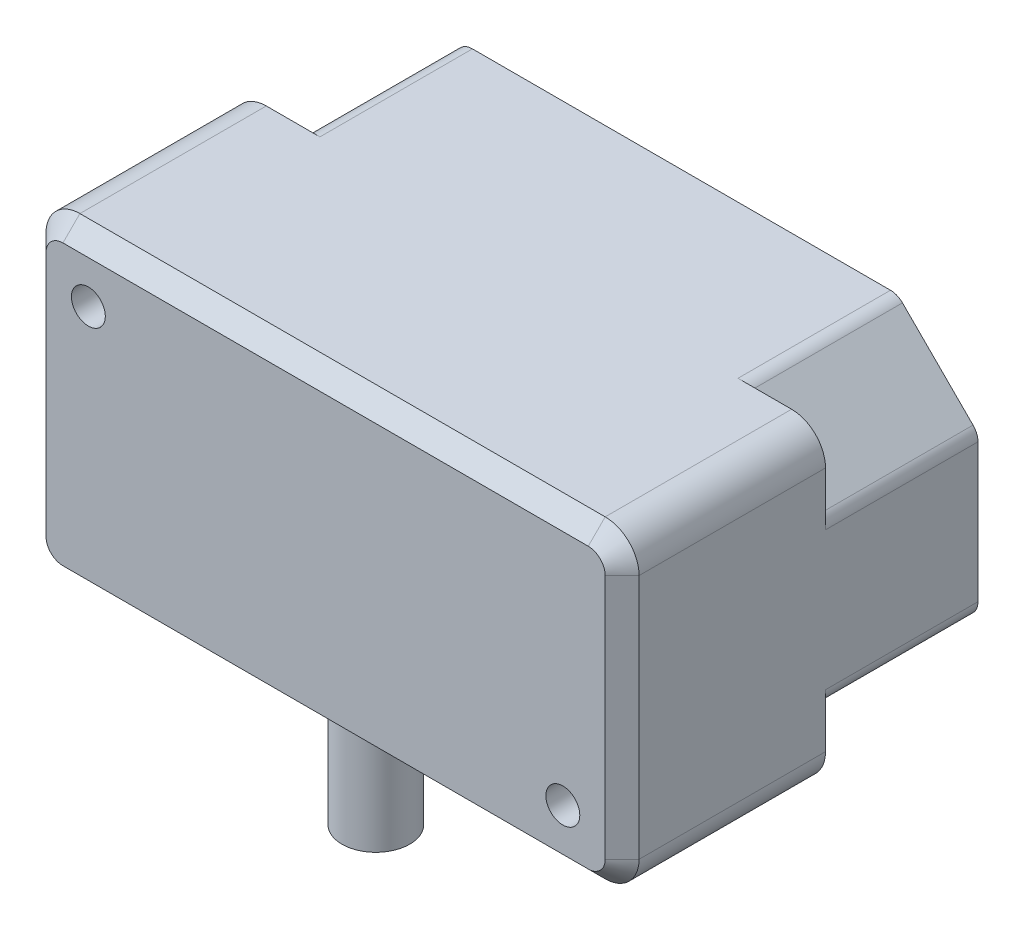
SolidWorks part; units mm, degrees
material "ABS"
ref_plane "Plan de face" through (0, 0, 0) normal (0, 0, 1) x (1, 0, 0)
ref_plane "Plan de dessus" through (0, 0, 0) normal (0, 1, 0) x (1, 0, 0)
ref_plane "Plan de droite" through (0, 0, 0) normal (1, 0, 0) x (0, 0, -1)
sketch "Esquisse1" plane through (0, 0, 0) normal (0, 0, 1) x (1, 0, 0)
  line L1 (17.5, 9.25) -> (-17.5, 9.25)
  line L2 (17.5, 9.25) -> (17.5, -9.25)
  line L3 (17.5, -9.25) -> (-17.5, -9.25)
  line L4 (-17.5, 9.25) -> (-17.5, -9.25)
  line L5 (17.5, 9.25) -> (-17.5, -9.25) construction
  line L6 (17.5, -9.25) -> (-17.5, 9.25) construction
  point P0 (0, 0)
  dimension "D1" = 18.5
  dimension "D2" = 35
extrude "Boss.-Extru.1" add sketch "Esquisse1" along normal blind 21
fillet "Congé1" radius 2 4 edges at (-17.5, -9.25, 10.5) (17.5, -9.25, 10.5) (-17.5, 9.25, 10.5) (17.5, 9.25, 10.5)
sketch "Esquisse2" plane through (0, 0, 21) normal (0, 0, 1) x (1, 0, 0)
  line L1 (14, 5.75) -> (-14, 5.75) construction
  line L2 (14, 5.75) -> (14, -5.75) construction
  line L3 (14, -5.75) -> (-14, -5.75) construction
  line L4 (-14, 5.75) -> (-14, -5.75) construction
  line L5 (14, 5.75) -> (-14, -5.75) construction
  line L6 (14, -5.75) -> (-14, 5.75) construction
  circle A1 centre (-14, 5.75) radius 1
  circle A3 centre (14, -5.75) radius 1
  point P0 (0, 0)
  dimension "D3" = 2
  dimension "D4" = 2
  dimension "D1" = 28
  dimension "D2" = 11.5
extrude "Enlèv. mat.-Extru.1" cut sketch "Esquisse2" against normal blind 4
sketch "Esquisse3" plane through (0, 0, 0) normal (0, 0, -1) x (-1, 0, 0)
  line L0 (-17.5, 4.5) -> (-12.75, 9.25)
  line L1 (-17.5, -7.25) -> (-17.5, 7.25) construction
  line L2 (-15.5, 9.25) -> (15.5, 9.25) construction
  line L3 (-12.75, 9.25) -> (12.75, 9.25)
  line L4 (-17.5, 0) -> (17.5, 0) construction
  line L5 (0, -9.25) -> (0, 9.25) construction
  line L6 (-17.5, 4.5) -> (-17.5, -4.5)
  line L7 (17.5, 4.5) -> (17.5, -4.5)
  line L8 (17.5, 4.5) -> (12.75, 9.25)
  line L9 (17.5, -4.5) -> (12.75, -9.25)
  line L10 (-12.75, -9.25) -> (12.75, -9.25)
  line L11 (-17.5, -4.5) -> (-12.75, -9.25)
  point P14 (0, 0)
  dimension "D1" = 45
  dimension "D2" = 4.5
extrude "Enlèv. mat.-Extru.2" cut sketch "Esquisse3" against normal blind 9 flip side to cut
fillet "Congé2" radius 1 8 edges at (17.5, -4.5, 4.5) (12.75, -9.25, 4.5) (-12.75, -9.25, 4.5) (-17.5, -4.5, 4.5) (-17.5, 4.5, 4.5) (-12.75, 9.25, 4.5) (12.75, 9.25, 4.5) (17.5, 4.5, 4.5)
sketch "Esquisse4" plane through (0, 0, 0) normal (0, 0, -1) x (-1, 0, 0)
  line L8 (0, -8.75) -> (0, 8.75) construction
  line L9 (-0.25, 8.75) -> (-0.25, -8.75)
  line L10 (0.25, 8.75) -> (0.25, -8.75)
  line L11 (0, 0) -> (5.2997, 0) construction
  line L12 (-0.25, 8.75) -> (-12.3358, 8.75)
  line L13 (0.25, -8.75) -> (12.3358, -8.75)
  line L16 (-17, 4.0858) -> (-17, -4.0858)
  line L17 (-16.8536, -4.4393) -> (-12.6893, -8.6036)
  line L18 (-12.3358, -8.75) -> (12.3358, -8.75)
  line L19 (12.6893, -8.6036) -> (16.8536, -4.4393)
  line L20 (17, -4.0858) -> (17, 4.0858)
  line L21 (16.8536, 4.4393) -> (12.6893, 8.6036)
  line L22 (12.3358, 8.75) -> (-12.3358, 8.75)
  line L23 (-12.6893, 8.6036) -> (-16.8536, 4.4393)
  line L24 (-17, 4.0858) -> (-17, -4.0858)
  line L25 (-16.8536, -4.4393) -> (-12.6893, -8.6036)
  line L26 (-12.3358, -8.75) -> (-0.25, -8.75)
  line L27 (12.6893, -8.6036) -> (16.8536, -4.4393)
  line L28 (17, -4.0858) -> (17, 4.0858)
  line L29 (16.8536, 4.4393) -> (12.6893, 8.6036)
  line L30 (12.3358, 8.75) -> (0.25, 8.75)
  line L31 (-12.6893, 8.6036) -> (-16.8536, 4.4393)
  arc A16 (-17, -4.0858) -> (-16.8536, -4.4393) centre (-16.5, -4.0858) ccw
  arc A17 (-12.6893, -8.6036) -> (-12.3358, -8.75) centre (-12.3358, -8.25) ccw
  arc A18 (12.3358, -8.75) -> (12.6893, -8.6036) centre (12.3358, -8.25) ccw
  arc A19 (16.8536, -4.4393) -> (17, -4.0858) centre (16.5, -4.0858) ccw
  arc A20 (17, 4.0858) -> (16.8536, 4.4393) centre (16.5, 4.0858) ccw
  arc A21 (12.6893, 8.6036) -> (12.3358, 8.75) centre (12.3358, 8.25) ccw
  arc A22 (-12.3358, 8.75) -> (-12.6893, 8.6036) centre (-12.3358, 8.25) ccw
  arc A23 (-16.8536, 4.4393) -> (-17, 4.0858) centre (-16.5, 4.0858) ccw
  arc A24 (-17, -4.0858) -> (-16.8536, -4.4393) centre (-16.5, -4.0858) ccw
  arc A25 (-12.6893, -8.6036) -> (-12.3358, -8.75) centre (-12.3358, -8.25) ccw
  arc A26 (12.3358, -8.75) -> (12.6893, -8.6036) centre (12.3358, -8.25) ccw
  arc A27 (16.8536, -4.4393) -> (17, -4.0858) centre (16.5, -4.0858) ccw
  arc A28 (17, 4.0858) -> (16.8536, 4.4393) centre (16.5, 4.0858) ccw
  arc A29 (12.6893, 8.6036) -> (12.3358, 8.75) centre (12.3358, 8.25) ccw
  arc A30 (-12.3358, 8.75) -> (-12.6893, 8.6036) centre (-12.3358, 8.25) ccw
  arc A31 (-16.8536, 4.4393) -> (-17, 4.0858) centre (-16.5, 4.0858) ccw
  point P9 (0.25, 0)
  point P10 (-0.25, 0)
  dimension "D2" = 0.5
  dimension "D1" = 0.5
extrude "Enlèv. mat.-Extru.3" cut sketch "Esquisse4" against normal blind 0.5
sketch "Esquisse5" plane through (0, -9.25, 0) normal (0, -1, 0) x (1, 0, 0)
  line L0 (-0.25, 0) -> (0, 21) construction
  line L1 (-15.5, 21) -> (15.5, 21) construction
  circle A0 centre (-0.0357, 18) radius 2
  dimension "D1" = 4
  dimension "D2" = 3
extrude "Boss.-Extru.2" add sketch "Esquisse5" along normal blind 6
chamfer "Chanfrein1" distance 1 angle 45 8 edges at (-16.9142, 8.6642, 21) (0, 9.25, 21) (16.9142, 8.6642, 21) (17.5, 0, 21) (16.9142, -8.6642, 21) (0, -9.25, 21) (-16.9142, -8.6642, 21) (-17.5, 0, 21)
